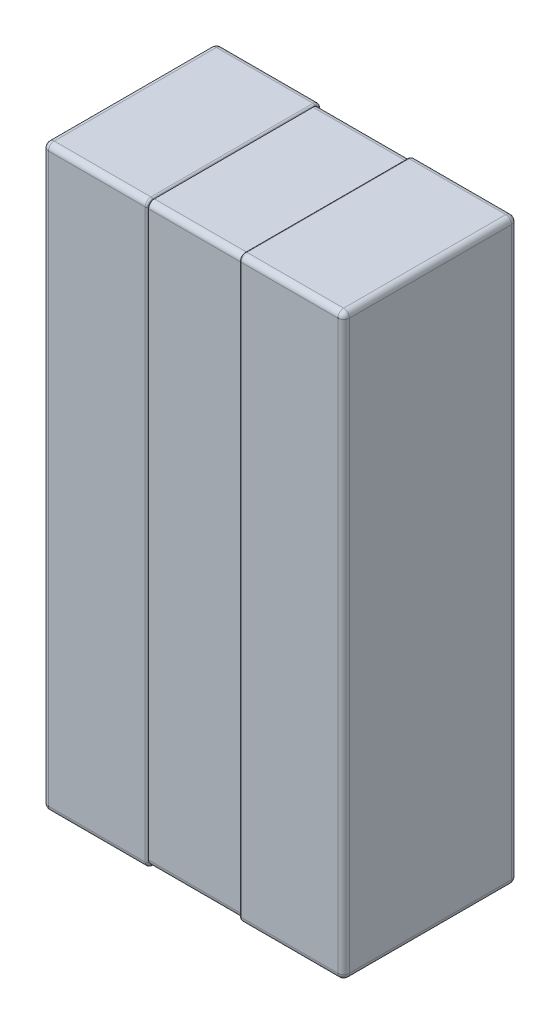
SolidWorks part; units mm, degrees
ref_plane "Top Plane" through (0, 0, 0) normal (0, 0, 1) x (1, 0, 0)
ref_plane "Front Plane" through (0, 0, 0) normal (0, 1, 0) x (1, 0, 0)
ref_plane "Side Plane" through (0, 0, 0) normal (1, 0, 0) x (0, 0, -1)
sketch "Sketch1" plane through (0, 0, 0) normal (0, 0, 1) x (1, 0, 0)
  line L1 (-0.26, 0.5) -> (0.26, 0.5)
  line L2 (-0.26, 0.5) -> (-0.26, -0.5)
  line L3 (-0.26, -0.5) -> (0.26, -0.5)
  line L4 (0.26, 0.5) -> (0.26, -0.5)
  dimension "D1" = 0.52
  dimension "D2" = 0.26
  dimension "D3" = 1
  dimension "D4" = 0.5
extrude "All body" add sketch "Sketch1" along normal blind 0.3
sketch "Sketch2" plane through (0, 0, 0) normal (1, 0, 0) x (0, 0, -1)
  line L14 (-0.003, 0.497) -> (-0.297, 0.497)
  line L15 (-0.003, -0.497) -> (-0.003, 0.497)
  line L16 (-0.297, -0.497) -> (-0.003, -0.497)
  line L17 (-0.297, 0.497) -> (-0.297, -0.497)
  line L18 (-0.003, 0.497) -> (-0.297, 0.497)
  line L19 (-0.003, -0.497) -> (-0.003, 0.497)
  line L20 (-0.297, -0.497) -> (-0.003, -0.497)
  line L21 (-0.297, 0.497) -> (-0.297, -0.497)
  dimension "D1" = 0.003
extrude "Cut out the body for pin" cut sketch "Sketch2" against normal blind 0.08 and the other way blind 0.08 flip side to cut
fillet "Body fillet" radius 0.01 4 edges at (0, 0.497, 0.003) (0, 0.497, 0.297) (0, -0.497, 0.003) (0, -0.497, 0.297)
fillet "Pin fillet a" radius 0.01 16 edges at (0.26, -0.5, 0.15) (0.26, 0, 0.3) (0.26, 0.5, 0.15) (0.26, 0, 0) (-0.26, 0.5, 0.15) (-0.26, 0, 0.3) (-0.26, -0.5, 0.15) (-0.26, 0, 0) (0.17, 0.5, 0.3) (0.17, -0.5, 0.3) (0.17, -0.5, 0) (0.17, 0.5, 0) (-0.17, 0.5, 0) (-0.17, -0.5, 0) (-0.17, 0.5, 0.3) (-0.17, -0.5, 0.3)
fillet "Pin fillet b" radius 0.003 16 edges at (0.08, -0.4971, 0.2971) (0.08, -0.5, 0.15) (0.08, -0.4971, 0.0029) (0.08, 0, 0) (0.08, 0.4971, 0.0029) (0.08, 0.5, 0.15) (0.08, 0.4971, 0.2971) (-0.08, -0.4971, 0.2971) (-0.08, -0.5, 0.15) (-0.08, -0.4971, 0.0029) (-0.08, 0, 0) (-0.08, 0.4971, 0.0029) (-0.08, 0.5, 0.15) (-0.08, 0.4971, 0.2971) (0.08, 0, 0.3) (-0.08, 0, 0.3)
